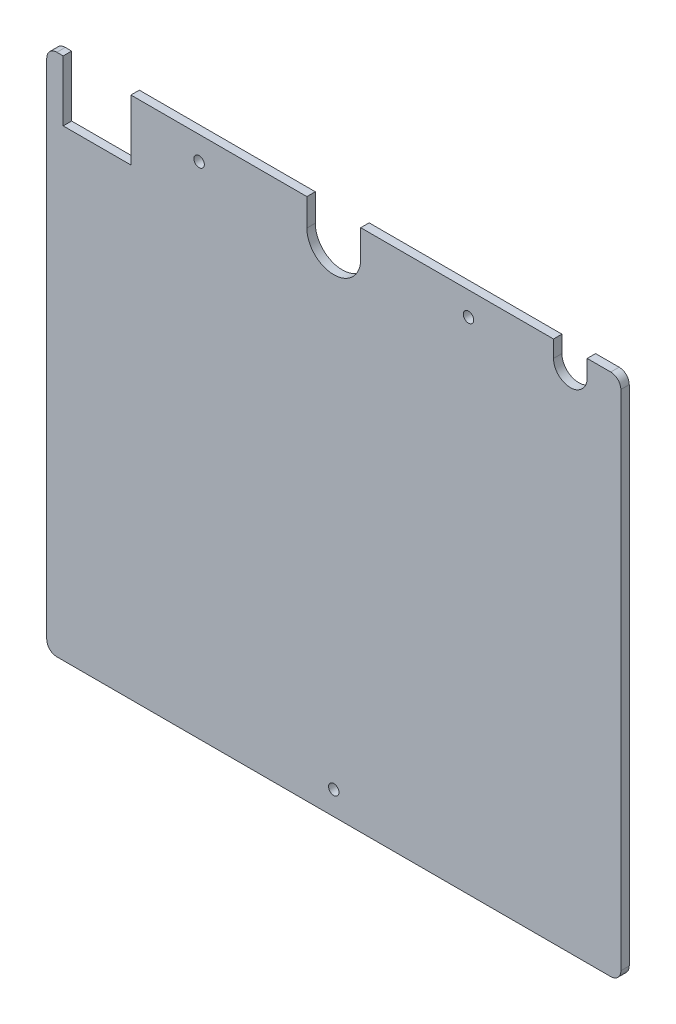
SolidWorks part; units mm, degrees
ref_plane "Plano frontal" through (0, 0, 0) normal (0, 0, 1) x (1, 0, 0)
ref_plane "Plano superior" through (0, 0, 0) normal (0, 1, 0) x (1, 0, 0)
ref_plane "Plano direito" through (0, 0, 0) normal (1, 0, 0) x (0, 0, -1)
sketch "Esboço1" plane through (0, 0, 0) normal (0, 0, 1) x (1, 0, 0)
  line L1 (-82.25, 77.75) -> (82.25, 77.75)
  line L2 (-85.25, 74.75) -> (-85.25, -74.75)
  line L3 (-82.25, -77.75) -> (82.25, -77.75)
  line L4 (85.25, 74.75) -> (85.25, -74.75)
  line L5 (-85.25, 77.75) -> (85.25, -77.75) construction
  line L6 (-85.25, -77.75) -> (85.25, 77.75) construction
  arc A0 (-85.25, -74.75) -> (-82.25, -77.75) centre (-82.25, -74.75) ccw
  arc A1 (82.25, -77.75) -> (85.25, -74.75) centre (82.25, -74.75) ccw
  arc A2 (82.25, 77.75) -> (85.25, 74.75) centre (82.25, 74.75) cw
  arc A3 (-82.25, 77.75) -> (-85.25, 74.75) centre (-82.25, 74.75) ccw
  point P0 (0, 0)
  dimension "D1" = 3
  dimension "D2" = 155.5
  dimension "D3" = 170.5
extrude "Ressalto-extrusão1" add sketch "Esboço1" along normal blind 2.5
sketch "Esboço2" plane through (0, 0, 2.5) normal (0, 0, 1) x (1, 0, 0)
  line L0 (8, 69.65) -> (8, 77.75)
  line L1 (82.25, 77.75) -> (-82.25, 77.75) construction
  line L2 (8, 77.75) -> (-8, 77.75)
  line L3 (-8, 77.75) -> (-8, 69.65)
  line L5 (-60.25, 77.75) -> (-80.3642, 77.75)
  line L6 (-60.25, 77.75) -> (-60.25, 59.75)
  line L7 (-60.25, 59.75) -> (-80.3642, 59.75)
  line L8 (-80.3642, 77.75) -> (-80.3642, 59.75)
  line L9 (85.25, -74.75) -> (85.25, 74.75) construction
  line L10 (65.25, 77.75) -> (75.25, 77.75)
  line L11 (65.25, 77.75) -> (65.25, 72.75)
  line L13 (75.25, 77.75) -> (75.25, 72.75)
  line L14 (-82.25, -77.75) -> (82.25, -77.75) construction
  line L15 (0, 0) -> (0, 27.1205) construction
  line L16 (-85.25, 74.75) -> (-85.25, -74.75) construction
  arc A0 (-8, 69.65) -> (8, 69.65) centre (0, 69.65) ccw
  arc A1 (65.25, 72.75) -> (75.25, 72.75) centre (70.25, 72.75) ccw
  circle A2 centre (0, -70.75) radius 1.55
  circle A3 centre (-40, 70.75) radius 1.55
  circle A4 centre (40, 70.75) radius 1.55
  dimension "D2" = 16
  dimension "D6" = 10
  dimension "D8" = 3.1
  dimension "D11" = 3.1
  dimension "D1" = 8.1
  dimension "D3" = 18
  dimension "D4" = 25
  dimension "D5" = 10
  dimension "D7" = 7
  dimension "D9" = 4.8858
  dimension "D10" = 7
  dimension "D12" = 80
extrude "Corte-extrusão1" cut sketch "Esboço2" against normal through all
